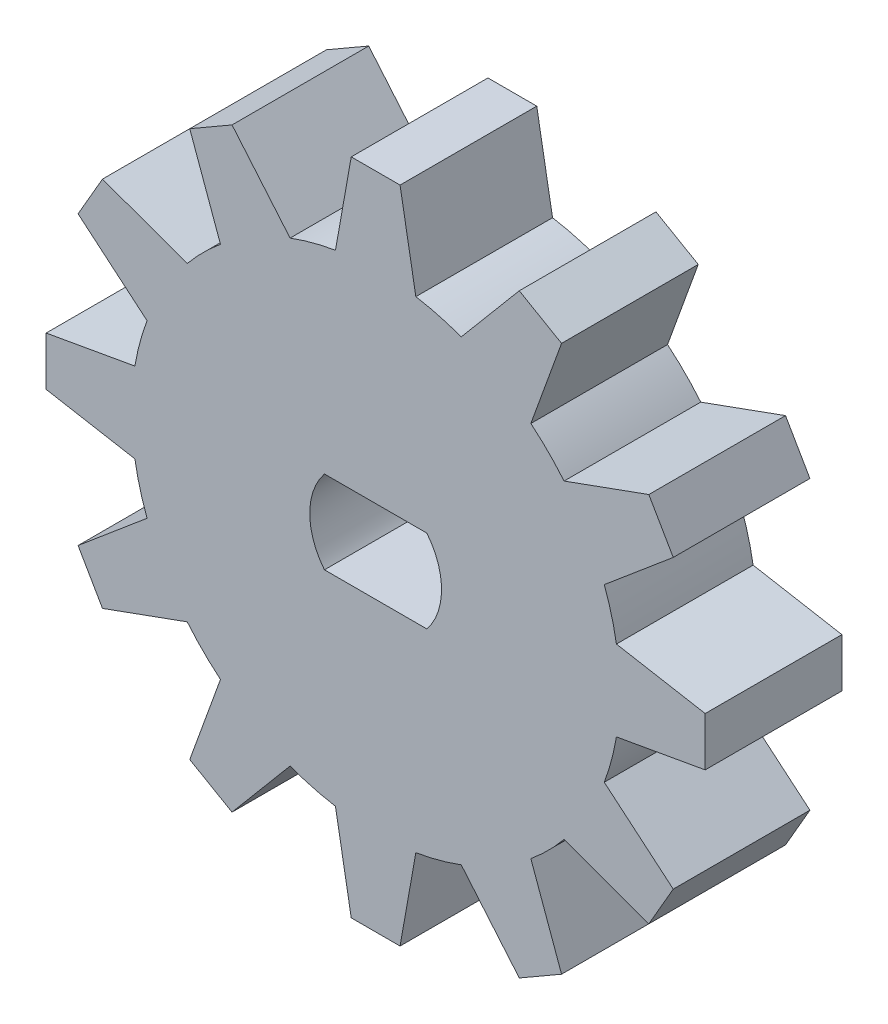
SolidWorks part; units mm, degrees
ref_plane "Front Plane" through (0, 0, 0) normal (0, 0, 1) x (1, 0, 0)
ref_plane "Top Plane" through (0, 0, 0) normal (0, 1, 0) x (1, 0, 0)
ref_plane "Right Plane" through (0, 0, 0) normal (1, 0, 0) x (0, 0, -1)
sketch "Sketch1" plane through (0, 0, 0) normal (0, 0, 1) x (1, 0, 0)
  circle A0 centre (0, 0) radius 10
  dimension "D1" = 20
extrude "Boss-Extrude1" add sketch "Sketch1" along normal blind 5.6
sketch "Sketch3" plane through (0, 0, 0) normal (0, 0, 1) x (1, 0, 0)
  line L0 (0, -13.5) -> (0, 13.5) construction
  line L1 (-1, 13.5) -> (1, 13.5)
  line L2 (-1, 13.5) -> (-1.8, 9)
  line L3 (-1.8, 9) -> (1.8, 9)
  line L4 (1.8, 9) -> (1, 13.5)
  point P3 (0, 0)
  point P4 (0, 9)
  point P6 (0, 13.5)
  dimension "D1" = 13.5
  dimension "D2" = 3.6
  dimension "D3" = 2
  dimension "D4" = 9
extrude "Boss-Extrude2" add sketch "Sketch3" along normal blind 5.6
ref_axis "Axis2" through (0, 0, 5.6) along (0, 0, -1)
pattern_circular "CirPattern1" count 12 every 30 about axis through (0, 0, 0) along (0, 0, 1) of "Boss-Extrude2"
sketch "Sketch4" plane through (0, 0, 0) normal (0, 0, 1) x (1, 0, 0)
  line L1 (-2.0976, -1.7) -> (2.0976, -1.7)
  line L2 (-2.0976, 1.7) -> (2.0976, 1.7)
  arc A1 (2.0976, -1.7) -> (2.0976, 1.7) centre (0, 0) ccw
  circle A2 centre (0, 0) radius 1.7 construction
  arc A3 (-2.0976, 1.7) -> (-2.0976, -1.7) centre (0, 0) ccw
  point P5 (0, -1.7)
  point P8 (0, 1.7)
  dimension "D2" = 2.7
  dimension "D3" = 3.4
extrude "Cut-Extrude1" cut sketch "Sketch4" along normal blind 7
sketch "Sketch5" plane through (0, 0, 5.6) normal (0, 0, 1) x (1, 0, 0)
  circle A0 centre (0, 0) radius 10
  dimension "D1" = 20
